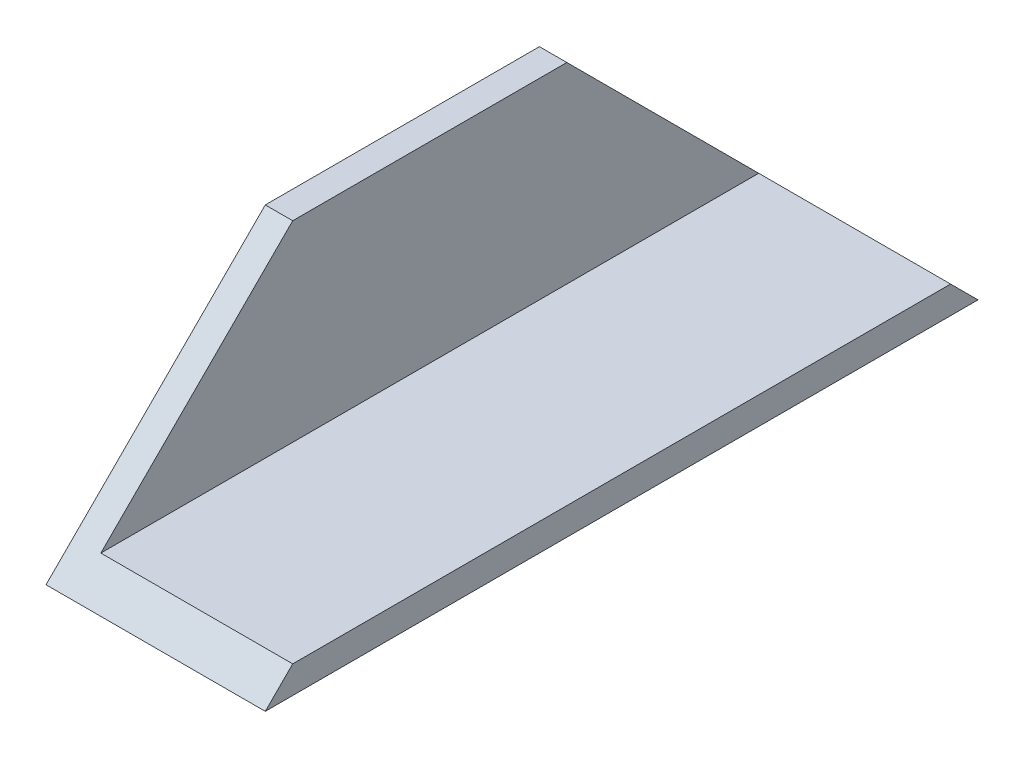
SolidWorks part; units mm, degrees
ref_plane "Front Plane" through (0, 0, 0) normal (0, 0, 1) x (1, 0, 0)
ref_plane "Top Plane" through (0, 0, 0) normal (0, 1, 0) x (1, 0, 0)
ref_plane "Right Plane" through (0, 0, 0) normal (1, 0, 0) x (0, 0, -1)
sketch "Sketch1" plane through (0, 0, 0) normal (0, 0, 1) x (1, 0, 0)
  line L0 (0, 25.4) -> (0, 0)
  line L1 (0, 0) -> (25.4, 0)
  line L2 (3.175, 25.4) -> (3.175, 3.175)
  line L3 (3.175, 3.175) -> (25.4, 3.175)
  line L4 (0, 25.4) -> (3.175, 25.4)
  line L5 (25.4, 3.175) -> (25.4, 0)
  dimension "D1" = 25.4
  dimension "D2" = 3.175
extrude "Boss-Extrude1" add sketch "Sketch1" along normal blind 82.55
chamfer "Chamfer1" distance 25.4 angle 45 2 edges at (1.5875, 25.4, 0) (1.5875, 25.4, 82.55)
